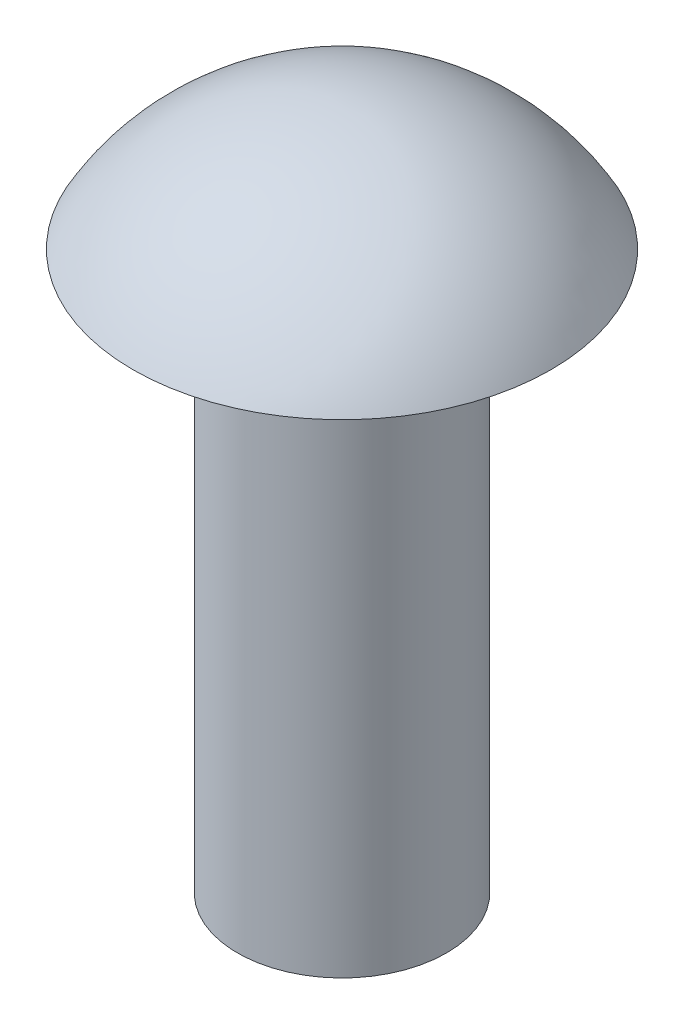
SolidWorks part; units mm, degrees
material "AISI 1020 Steel, Cold Rolled"
ref_plane "前视基准面" through (0, 0, 0) normal (0, 0, 1) x (1, 0, 0)
ref_plane "上视基准面" through (0, 0, 0) normal (0, 1, 0) x (1, 0, 0)
ref_plane "右视基准面" through (0, 0, 0) normal (1, 0, 0) x (0, 0, -1)
sketch "Sketch1" plane through (0, 0, 0) normal (0, 0, 1) x (1, 0, 0)
  line L0 (0, 0) -> (0, 1.75)
  line L1 (0, 0) -> (3, 0)
  line L2 (0, -1000) -> (0, 49000) construction
  arc A0 (0, 1.75) -> (3, 0) centre (0, -1.6964) cw
  point P7 (0.016, -1.669)
  dimension "D1" = 1.75
  dimension "D2" = 3
  dimension "D3" = 0
revolve "Revolve1" add sketch "Sketch1" angle 360 about L2
sketch "Sketch2" plane through (0, 0, 0) normal (0, -1, 0) x (1, 0, 0)
  circle A0 centre (0, 0) radius 1.5
  dimension "D1" = 3
extrude "Boss-Extrude1" add sketch "Sketch2" along normal blind 8
